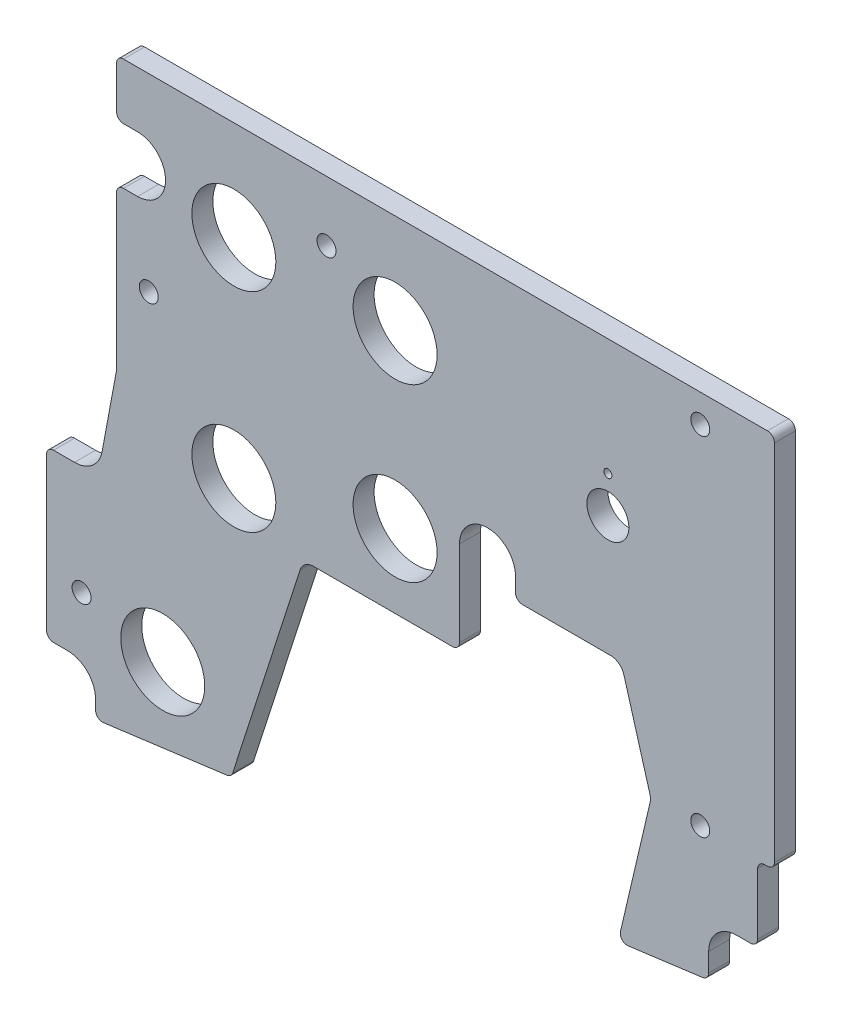
SolidWorks part; units mm, degrees
ref_plane "Front Plane" through (0, 0, 0) normal (0, 0, 1) x (1, 0, 0)
ref_plane "Top Plane" through (0, 0, 0) normal (0, 1, 0) x (1, 0, 0)
ref_plane "Right Plane" through (0, 0, 0) normal (1, 0, 0) x (0, 0, -1)
sketch "Sketch1" plane through (0, 0, 0) normal (0, 0, 1) x (1, 0, 0)
  line L24 (-1.5875, -85.5345) -> (-1.5875, -3.175)
  line L25 (-3.175, -1.5875) -> (-149.225, -1.5875)
  line L26 (-150.8125, -3.175) -> (-150.8125, -12.7)
  line L27 (-149.225, -14.2875) -> (-146.05, -14.2875)
  line L28 (-146.05, -26.9875) -> (-149.225, -26.9875)
  line L29 (-150.8125, -28.575) -> (-150.8125, -63.3539)
  line L30 (-150.8392, -63.6437) -> (-154.0942, -81.1696)
  line L31 (-160.3375, -86.36) -> (-165.1, -86.36)
  line L32 (-166.6875, -87.9475) -> (-166.6875, -122.5455)
  line L33 (-165.1, -124.133) -> (-161.925, -124.133)
  line L34 (-155.575, -130.483) -> (-155.575, -132.6404)
  line L35 (-153.7803, -134.2144) -> (-125.7711, -130.5269)
  line L36 (-124.467, -129.4389) -> (-109.1805, -81.8956)
  line L37 (-106.1579, -79.6925) -> (-74.6125, -79.6925)
  line L38 (-73.025, -78.105) -> (-73.025, -58.7375)
  line L39 (-60.325, -58.7375) -> (-60.325, -61.9125)
  line L40 (-58.7375, -63.5) -> (-38.7866, -63.5)
  line L41 (-35.7358, -65.7958) -> (-29.8313, -86.2841)
  line L42 (-29.7909, -87.8878) -> (-36.5223, -116.6102)
  line L43 (-34.7695, -118.5463) -> (-17.8903, -116.3241)
  line L44 (-16.51, -114.7502) -> (-16.51, -110.5169)
  line L45 (-10.16, -104.1528) -> (-6.985, -104.1528)
  line L46 (-5.3975, -102.5653) -> (-5.3975, -88.7095)
  line L47 (-3.81, -87.122) -> (-3.175, -87.122)
  line L48 (-1.5875, -85.5345) -> (-1.5875, -3.175)
  line L49 (-3.175, -1.5875) -> (-149.225, -1.5875)
  line L50 (-150.8125, -3.175) -> (-150.8125, -12.7)
  line L51 (-149.225, -14.2875) -> (-146.05, -14.2875)
  line L52 (-146.05, -26.9875) -> (-149.225, -26.9875)
  line L53 (-150.8125, -28.575) -> (-150.8125, -63.3539)
  line L54 (-150.8392, -63.6437) -> (-154.0942, -81.1696)
  line L55 (-160.3375, -86.36) -> (-165.1, -86.36)
  line L56 (-166.6875, -87.9475) -> (-166.6875, -122.5455)
  line L57 (-165.1, -124.133) -> (-161.925, -124.133)
  line L58 (-155.575, -130.483) -> (-155.575, -132.6404)
  line L59 (-153.7803, -134.2144) -> (-125.7711, -130.5269)
  line L60 (-124.467, -129.4389) -> (-109.1805, -81.8956)
  line L61 (-106.1579, -79.6925) -> (-74.6125, -79.6925)
  line L62 (-73.025, -78.105) -> (-73.025, -58.7375)
  line L63 (-60.325, -58.7375) -> (-60.325, -61.9125)
  line L64 (-58.7375, -63.5) -> (-38.7866, -63.5)
  line L65 (-35.7358, -65.7958) -> (-29.8313, -86.2841)
  line L66 (-29.7909, -87.8878) -> (-36.5223, -116.6102)
  line L67 (-34.7695, -118.5463) -> (-17.8903, -116.3241)
  line L68 (-16.51, -114.7502) -> (-16.51, -110.5169)
  line L69 (-10.16, -104.1528) -> (-6.985, -104.1528)
  line L70 (-5.3975, -102.5653) -> (-5.3975, -88.7095)
  line L71 (-3.81, -87.122) -> (-3.175, -87.122)
  arc A24 (-3.175, -87.122) -> (-1.5875, -85.5345) centre (-3.175, -85.5345) ccw
  arc A25 (-1.5875, -3.175) -> (-3.175, -1.5875) centre (-3.175, -3.175) ccw
  arc A26 (-149.225, -1.5875) -> (-150.8125, -3.175) centre (-149.225, -3.175) ccw
  arc A27 (-150.8125, -12.7) -> (-149.225, -14.2875) centre (-149.225, -12.7) ccw
  arc A28 (-146.05, -26.9875) -> (-146.05, -14.2875) centre (-146.05, -20.6375) ccw
  arc A29 (-149.225, -26.9875) -> (-150.8125, -28.575) centre (-149.225, -28.575) ccw
  arc A30 (-150.8392, -63.6437) -> (-150.8125, -63.3539) centre (-152.4, -63.3539) ccw
  arc A31 (-160.3375, -86.36) -> (-154.0942, -81.1696) centre (-160.3375, -80.01) ccw
  arc A32 (-165.1, -86.36) -> (-166.6875, -87.9475) centre (-165.1, -87.9475) ccw
  arc A33 (-166.6875, -122.5455) -> (-165.1, -124.133) centre (-165.1, -122.5455) ccw
  arc A34 (-155.575, -130.483) -> (-161.925, -124.133) centre (-161.925, -130.483) ccw
  arc A35 (-155.575, -132.6404) -> (-153.7803, -134.2144) centre (-153.9875, -132.6404) ccw
  arc A36 (-125.7711, -130.5269) -> (-124.467, -129.4389) centre (-125.9783, -128.953) ccw
  arc A37 (-106.1579, -79.6925) -> (-109.1805, -81.8956) centre (-106.1579, -82.8675) ccw
  arc A38 (-74.6125, -79.6925) -> (-73.025, -78.105) centre (-74.6125, -78.105) ccw
  arc A39 (-60.325, -58.7375) -> (-73.025, -58.7375) centre (-66.675, -58.7375) ccw
  arc A40 (-60.325, -61.9125) -> (-58.7375, -63.5) centre (-58.7375, -61.9125) ccw
  arc A41 (-35.7358, -65.7958) -> (-38.7866, -63.5) centre (-38.7866, -66.675) ccw
  arc A42 (-29.7909, -87.8878) -> (-29.8313, -86.2841) centre (-32.8822, -87.1633) ccw
  arc A43 (-36.5223, -116.6102) -> (-34.7695, -118.5463) centre (-34.9767, -116.9724) ccw
  arc A44 (-17.8903, -116.3241) -> (-16.51, -114.7502) centre (-18.0975, -114.7502) ccw
  arc A45 (-10.16, -104.1528) -> (-16.51, -110.5169) centre (-10.16, -110.5028) ccw
  arc A46 (-6.985, -104.1528) -> (-5.3975, -102.5653) centre (-6.985, -102.5653) ccw
  arc A47 (-3.81, -87.122) -> (-5.3975, -88.7095) centre (-3.81, -88.7095) ccw
  arc A48 (-3.175, -87.122) -> (-1.5875, -85.5345) centre (-3.175, -85.5345) ccw
  arc A49 (-1.5875, -3.175) -> (-3.175, -1.5875) centre (-3.175, -3.175) ccw
  arc A50 (-149.225, -1.5875) -> (-150.8125, -3.175) centre (-149.225, -3.175) ccw
  arc A51 (-150.8125, -12.7) -> (-149.225, -14.2875) centre (-149.225, -12.7) ccw
  arc A52 (-146.05, -26.9875) -> (-146.05, -14.2875) centre (-146.05, -20.6375) ccw
  arc A53 (-149.225, -26.9875) -> (-150.8125, -28.575) centre (-149.225, -28.575) ccw
  arc A54 (-150.8392, -63.6437) -> (-150.8125, -63.3539) centre (-152.4, -63.3539) ccw
  arc A55 (-160.3375, -86.36) -> (-154.0942, -81.1696) centre (-160.3375, -80.01) ccw
  arc A56 (-165.1, -86.36) -> (-166.6875, -87.9475) centre (-165.1, -87.9475) ccw
  arc A57 (-166.6875, -122.5455) -> (-165.1, -124.133) centre (-165.1, -122.5455) ccw
  arc A58 (-155.575, -130.483) -> (-161.925, -124.133) centre (-161.925, -130.483) ccw
  arc A59 (-155.575, -132.6404) -> (-153.7803, -134.2144) centre (-153.9875, -132.6404) ccw
  arc A60 (-125.7711, -130.5269) -> (-124.467, -129.4389) centre (-125.9783, -128.953) ccw
  arc A61 (-106.1579, -79.6925) -> (-109.1805, -81.8956) centre (-106.1579, -82.8675) ccw
  arc A62 (-74.6125, -79.6925) -> (-73.025, -78.105) centre (-74.6125, -78.105) ccw
  arc A63 (-60.325, -58.7375) -> (-73.025, -58.7375) centre (-66.675, -58.7375) ccw
  arc A64 (-60.325, -61.9125) -> (-58.7375, -63.5) centre (-58.7375, -61.9125) ccw
  arc A65 (-35.7358, -65.7958) -> (-38.7866, -63.5) centre (-38.7866, -66.675) ccw
  arc A66 (-29.7909, -87.8878) -> (-29.8313, -86.2841) centre (-32.8822, -87.1633) ccw
  arc A67 (-36.5223, -116.6102) -> (-34.7695, -118.5463) centre (-34.9767, -116.9724) ccw
  arc A68 (-17.8903, -116.3241) -> (-16.51, -114.7502) centre (-18.0975, -114.7502) ccw
  arc A69 (-10.16, -104.1528) -> (-16.51, -110.5169) centre (-10.16, -110.5028) ccw
  arc A70 (-6.985, -104.1528) -> (-5.3975, -102.5653) centre (-6.985, -102.5653) ccw
  arc A71 (-3.81, -87.122) -> (-5.3975, -88.7095) centre (-3.81, -88.7095) ccw
  dimension "D1" = 0
extrude "Boss-Extrude1" add sketch "Sketch1" along normal blind 4.7625
hole_wizard "#6 Clearance Hole1" positions "Sketch3" profile "Sketch2" hole size "#6" standard "ANSI Inch" end condition through all
sketch "Sketch3" plane through (0, 0, 4.7625) normal (0, 0, 1) x (1, 0, 0)
  point P0 (-103.1875, -15.24)
  point P3 (-18.415, -7.9375)
  point P6 (-143.51, -44.45)
  point P9 (-158.75, -111.125)
  point P12 (-18.415, -86.741)
sketch "Sketch2" plane through (-103.1875, -15.24, 4.7625) normal (1, 0, 0) x (0, -1, 0)
  line L0 (0, 0) -> (0, 4.7625)
  line L1 (0, 4.7625) -> (2.1526, 4.7625)
  line L2 (2.1526, 4.7625) -> (2.1526, 0)
  line L5 (2.1526, 0) -> (0, 0)
  line L11 (0, -6.35) -> (0, 107.95) construction
  dimension "Thru Hole Dia." = 4.3053
  dimension "Thru Hole Depth" = 4.7625
sketch "Sketch5" plane through (0, 0, 4.7625) normal (0, 0, 1) x (1, 0, 0)
  circle A0 centre (-124.206, -24.13) radius 9.525
  circle A1 centre (-87.63, -24.13) radius 9.525
  circle A2 centre (-87.63, -62.992) radius 9.525
  circle A3 centre (-124.206, -71.4375) radius 9.525
  circle A4 centre (-140.335, -115.57) radius 9.525
  circle A5 centre (-39.37, -36.322) radius 4.7625
  dimension "D1" = 19.05
  dimension "D2" = 9.525
extrude "Cut-Extrude1" cut sketch "Sketch5" against normal through all
hole_wizard "#0 Clearance Hole1" positions "Sketch6" profile "Sketch7" hole size "#0" standard "ANSI Inch" end condition through all
sketch "Sketch6" plane through (0, 0, 6.35) normal (0, 0, 1) x (1, 0, 0)
  point P0 (-39.37, -28.067)
sketch "Sketch7" plane through (-39.37, -28.067, 6.35) normal (1, 0, 0) x (0, -1, 0)
  line L0 (0, 0) -> (0, 6.35)
  line L1 (0, 6.35) -> (0.9271, 6.35)
  line L2 (0.9271, 6.35) -> (0.9271, 0)
  line L3 (0.9271, 0) -> (0, 0)
  line L4 (0, -6.35) -> (0, 107.95) construction
  dimension "Thru Hole Dia." = 1.8542
  dimension "Thru Hole Depth" = 6.35
